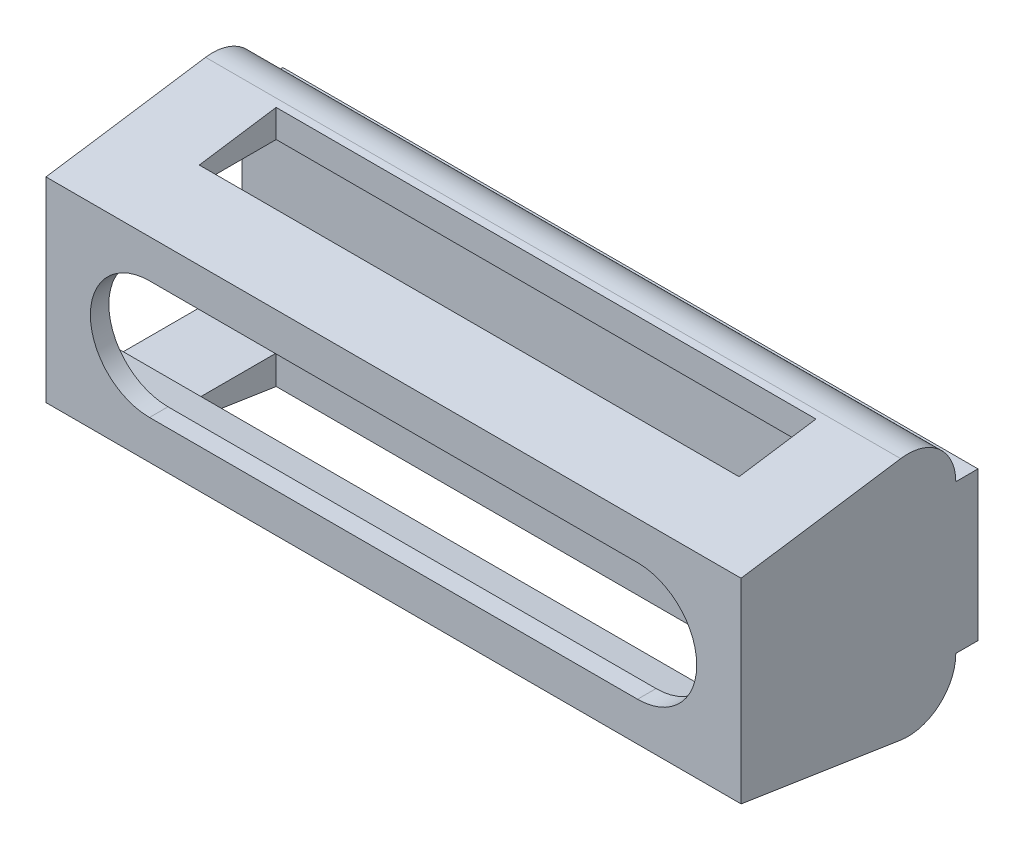
SolidWorks part; units mm, degrees
material "1060-H12"
ref_plane "Front Plane" through (0, 0, 0) normal (0, 0, 1) x (1, 0, 0)
ref_plane "Top Plane" through (0, 0, 0) normal (0, 1, 0) x (1, 0, 0)
ref_plane "Right Plane" through (0, 0, 0) normal (1, 0, 0) x (0, 0, -1)
sketch "Sketch19" plane through (0, 0, 0) normal (1, 0, 0) x (0, 0, -1)
  line L0 (-24.0388, 9.5506) -> (-4.5888, 12.4506)
  line L1 (-24.0388, 9.5506) -> (-24.0388, -9.5494)
  line L2 (-24.0388, -9.5494) -> (-4.6088, -12.5414)
  line L3 (0, 8.588) -> (0, -8.588)
  line L4 (-24.0388, 0.0006) -> (0, 0) construction
  arc A0 (-4.6088, -12.5414) -> (0, -8.588) centre (-4, -8.588) ccw
  arc A2 (0, 8.588) -> (-4.5888, 12.4506) centre (-3.9989, 8.4944) ccw
  dimension "D4" = 4
  dimension "D5" = 4
  dimension "D1" = 19.1
  dimension "D2" = 19.45
  dimension "D3" = 19.43
  dimension "D6" = 2.9
  dimension "D7" = 90.001
sketch "Sketch1" plane through (0, 0, 0) normal (0, 0, 1) x (1, 0, 0)
  line L1 (-46, 13) -> (46, 13)
  line L2 (-46, 13) -> (-46, -13)
  line L3 (-46, -13) -> (46, -13)
  line L4 (46, 13) -> (46, -13)
  line L5 (-46, 13) -> (46, -13) construction
  line L6 (-46, -13) -> (46, 13) construction
  point P0 (0, 0)
  dimension "D1" = 92
  dimension "D2" = 26
sketch "Sketch20" plane through (0, 0, 0) normal (1, 0, 0) x (0, 0, -1)
  line L0 (-26.5388, 13.2221) -> (-26.5388, -13.2116)
  line L1 (-26.5388, -13.2116) -> (-4.9893, -16.53)
  line L2 (-24.0388, 9.5506) -> (-24.0388, -9.5494) construction
  line L3 (-24.0388, -9.5494) -> (-4.6088, -12.5414) construction
  line L4 (-26.5388, 13.2221) -> (-4.9586, 16.4397)
  line L5 (-24.0388, 9.5506) -> (-4.5888, 12.4506) construction
  line L6 (2.5, 10.0108) -> (2.5, -10.1057)
  line L7 (0, 8.588) -> (0, -8.588) construction
  arc A0 (-4.9893, -16.53) -> (2.5, -10.1057) centre (-4, -10.1057) ccw
  arc A2 (2.5, 10.0108) -> (-4.9586, 16.4397) centre (-4, 10.0108) ccw
  dimension "D5" = 6.5
  dimension "D6" = 13
  dimension "D1" = 2.5
  dimension "D2" = 4
  dimension "D3" = 4
  dimension "D4" = 2.5
extrude "Boss-Extrude4" add sketch "Sketch20" along normal blind 47 and the other way blind 47 contours L4 A2 L6 A0 L1 L0
extrude "Cut-Extrude1" cut sketch "Sketch19" against normal through all and the other way blind 46
sketch "Sketch21" plane through (0, 0, 26.5388) normal (0, 0, 1) x (1, 0, 0)
  line L1 (-33, 8.0506) -> (33, 8.0506)
  line L3 (-33, -7.9494) -> (33, -7.9494)
  arc A0 (-33, 8.0506) -> (-33, -7.9494) centre (-33, 0.0506) ccw
  arc A1 (33, -7.9494) -> (33, 8.0506) centre (33, 0.0506) ccw
  dimension "D3" = 66
  dimension "D1" = 16
  dimension "D2" = 1.5
  dimension "D4" = 33
extrude "Cut-Extrude2" cut sketch "Sketch21" against normal up to surface (2.5 mm away) and the other way through all up to face at (-0.5, 0.0006, 24.0388)
sketch "Sketch22" plane through (0, 0, 0) normal (0, 1, 0) x (1, 0, 0)
  line L0 (-47, -26.5388) -> (-47, -4.9586) construction
  line L1 (-36.5, -16.3088) -> (36.5, -16.3088)
  line L2 (-36.5, -16.3088) -> (-36.5, -5.9088)
  line L3 (-36.5, -5.9088) -> (36.5, -5.9088)
  line L4 (36.5, -16.3088) -> (36.5, -5.9088)
  line L5 (-47, -26.5388) -> (47, -26.5388) construction
  line L6 (47, -26.5388) -> (47, -4.9586) construction
  dimension "D1" = 10.5
  dimension "D2" = 10.23
  dimension "D3" = 10.4
  dimension "D4" = 10.5
extrude "Cut-Extrude3" cut sketch "Sketch22" against normal through all both and the other way through all
ref_plane "Plane1" through (46, 0, 0) normal (-1, 0, 0) x (0, 0, 1)
sketch "Sketch26" plane through (46, 0, 0) normal (-1, 0, 0) x (0, 0, 1)
  line L0 (18.0988, -10.4641) -> (18.0988, -12.4741)
  line L1 (24.0388, -9.5494) -> (4.6088, -12.5414) construction
  line L2 (24.0388, 9.5506) -> (24.0388, -9.5494) construction
  line L3 (18.0988, -12.4741) -> (3.6288, -12.4741)
  line L4 (18.0988, -10.4641) -> (18.0988, 10.4363)
  line L5 (4.5888, 12.4506) -> (24.0388, 9.5506) construction
  line L6 (18.0988, 10.4363) -> (18.0988, 12.5363)
  line L7 (18.0988, 12.5363) -> (3.6697, 12.5363)
  line L8 (3.6697, 12.5363) -> (3.6288, -12.4741)
  dimension "D1" = 5.94
  dimension "D2" = 2.01
  dimension "D3" = 2.1
  dimension "D4" = 14.47
extrude "Cut-Extrude6" cut sketch "Sketch26" along normal up to surface (93 mm away) up to face at (-47, -0.0312, 9.1793)
sketch "Sketch27" plane through (0, 0, 0) normal (1, 0, 0) x (0, 0, -1)
  line L1 (2.5, 10.0108) -> (5.5, 10.0108)
  line L2 (2.5, 10.0108) -> (2.5, -10.1057)
  line L3 (2.5, -10.1057) -> (5.5, -10.1057)
  line L4 (5.5, 10.0108) -> (5.5, -10.1057)
  line L5 (2.5, 10.0108) -> (5.5, -10.1057) construction
  line L6 (2.5, -10.1057) -> (5.5, 10.0108) construction
  point P4 (4, -0.0475)
  dimension "D1" = 3
extrude "Boss-Extrude5" add sketch "Sketch27" along normal up to surface (47 mm away) and the other way up to surface (47 mm away) contours L3 L4 L1 L2 up to face at (47, -0.0312, 9.1793) other way up to face at (-47, -0.0312, 9.1793)
sketch "Sketch28" plane through (0, 0, -5.5) normal (0, 0, -1) x (-1, 0, 0)
  line L0 (0, 0) -> (-24, 0) construction
  line L1 (0, 0) -> (24, 0) construction
  circle A0 centre (-24, 0) radius 2
  circle A1 centre (24, 0) radius 2
  dimension "D3" = 4
  dimension "D1" = 24
  dimension "D2" = 24
extrude "Cut-Extrude7" cut sketch "Sketch28" against normal blind 4
sketch "Sketch31" plane through (0, 0, 0) normal (1, 0, 0) x (0, 0, -1)
  line L0 (-4, 16.5108) -> (5.5, 16.5108) construction
  line L1 (5.5, 16.5108) -> (5.5, -16.6057) construction
  line L2 (5.5, -16.6057) -> (-4, -16.6057) construction
  line L3 (5.5, 10.0108) -> (5.5, -10.1057) construction
  arc A0 (2.5, 10.0108) -> (-4.9586, 16.4397) centre (-4, 10.0108) ccw construction
  arc A1 (-4.9893, -16.53) -> (2.5, -10.1057) centre (-4, -10.1057) ccw construction
  dimension "D1" = 16.5108
  dimension "D2" = 16.6057
sketch "Sketch32" plane through (0, 0, 0) normal (0, 0, 1) x (1, 0, 0)
  line L0 (24, 0) -> (-24, 0) construction
  line L2 (47, 10.0108) -> (-47, 10.0108)
  line L3 (47, 10.0108) -> (47, -10.1057)
  line L4 (47, -10.1057) -> (-47, -10.1057)
  line L5 (-47, 10.0108) -> (-47, -10.1057)
  line L6 (47, 10.0108) -> (-47, -10.1057) construction
  line L7 (47, -10.1057) -> (-47, 10.0108) construction
  point P8 (0, -0.0475)
  dimension "D1" = 94
  dimension "D2" = 20.1165
  dimension "D3" = 10.1057
